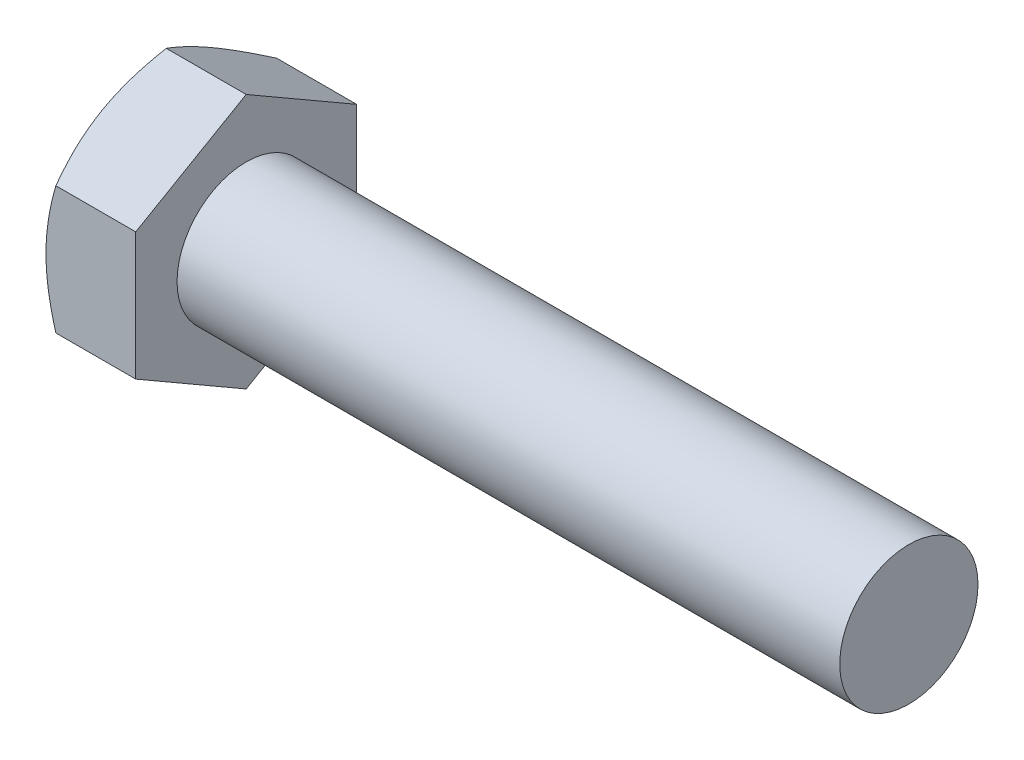
SolidWorks part; units mm, degrees
material "Alloy Steel"
ref_plane "Front Plane" through (0, 0, 0) normal (0, 0, 1) x (1, 0, 0)
ref_plane "Top Plane" through (0, 0, 0) normal (0, 1, 0) x (1, 0, 0)
ref_plane "Right Plane" through (0, 0, 0) normal (1, 0, 0) x (0, 0, -1)
sketch "Sketch1" plane through (0, 0, 0) normal (0, 0, 1) x (1, 0, 0)
  line L0 (-21.6297, 0) -> (21.6297, 0) construction
  line L1 (21.6297, 3.9751) -> (21.6297, -3.9751) construction
  line L2 (-16.4703, 6.35) -> (-16.4703, -6.35) construction
  line L3 (-21.6297, 6.35) -> (-21.6297, -6.35) construction
  point P9 (-16.4703, 0)
  point P10 (17.9255, -3.9751)
  point P11 (8.1359, 0)
  dimension "D1" = 3.7042
ref_plane "Plane2" through (21.6297, 0, 0) normal (1, 0, 0) x (0, 0, -1)
sketch "Sketch5" plane through (21.6297, 0, 0) normal (1, 0, 0) x (0, 0, -1)
  circle A0 centre (0, 0) radius 3.9751
extrude "Boss-Extrude3" add sketch "Sketch5" against normal up to vertex (38.1 mm away) up to point (-16.4703, 0, 0)
sketch "Sketch6" plane through (-16.4703, 0, 0) normal (-1, 0, 0) x (0, 0, 1)
  line L0 (0, 6.35) -> (0, -6.35) construction
  line L1 (6.35, 3.6662) -> (0, 7.3323)
  line L2 (0, 7.3323) -> (-6.35, 3.6662)
  line L3 (-6.35, 3.6662) -> (-6.35, -3.6662)
  line L4 (-6.35, -3.6662) -> (0, -7.3323)
  line L5 (0, -7.3323) -> (6.35, -3.6662)
  line L6 (6.35, -3.6662) -> (6.35, 3.6662)
  circle A0 centre (0, 0) radius 6.35 construction
extrude "Boss-Extrude4" add sketch "Sketch6" along normal up to vertex (5.1594 mm away) up to point (-21.6297, -6.35, 0)
sketch "Sketch7" plane through (-21.6297, 0, 0) normal (-1, 0, 0) x (0, 0, 1)
  circle A0 centre (0, 0) radius 6.35 construction
  circle A1 centre (0, 0) radius 6.35
sketch "Sketch12" plane through (-21.6297, 0, 0) normal (-1, 0, 0) x (0, 0, 1)
  line L0 (0, 4.8895) -> (0, 2.7305) construction
  line L1 (0.1905, 4.8895) -> (0.1905, 2.7305)
  line L2 (-0.1905, 4.8895) -> (-0.1905, 2.7305)
  line L3 (0, 3.9751) -> (0, -3.9751) construction
  arc A0 (0.1905, 4.8895) -> (-0.1905, 4.8895) centre (0, 4.8895) ccw
  arc A1 (-0.1905, 2.7305) -> (0.1905, 2.7305) centre (0, 2.7305) ccw
  circle A3 centre (0, 0) radius 2.54 construction
  circle A4 centre (0, 0) radius 5.08 construction
  point P2 (0, 3.81)
  dimension "D3" = 10.16
  dimension "D2" = 0.381
sketch "Sketch8" plane through (-21.6297, 0, 0) normal (-1, 0, 0) x (0, 0, 1)
  circle A0 centre (0, 0) radius 6.35 construction
  circle A1 centre (0, 0) radius 6.35
extrude "Cut-Extrude3" cut sketch "Sketch8" against normal through all draft 60 flip side to cut
sketch "Sketch13" plane through (0, 0, 0) normal (0, 0, 1) x (1, 0, 0)
  line L0 (17.2545, 0) -> (0, 0) construction
  circle A0 centre (17.2545, 0) radius 0.9652
  dimension "Hole Dia" = 1.9304
  dimension "Hole Distance" = 9.1186
extrude "Cotter Pin Hole" [suppressed] cut sketch "Sketch13" against normal through all and the other way through all
ref_plane "Split Plane" through (8.1359, 0, 0) normal (1, 0, 0) x (0, 0, -1)
ref_axis "Center Axis 1" through (-21.6297, 0, 0) along (1, 0, 0)
ref_plane "Contact Plane 1" through (-16.4703, 0, 0) normal (1, 0, 0) x (0, 0, -1)
split "Split1" [suppressed] bodies to split 118
sketch "Sketch9" [suppressed] plane through (22.8203, 0, 0) normal (1, 0, 0) x (0, 0, -1)
  circle A1 centre (0, 0) radius 3.9751
  circle A2 centre (0, 0) radius 3.9751
  dimension "D1" = 0
curve "Helix/Spiral1" [suppressed] pitch 1.0583 height 14.5521 turns 13.75 parameters "Pitch"=1.0583
chamfer "Chamfer1" [suppressed] distance 0.7938 angle 45
sketch "Sketch10" [suppressed] plane through (0, 0, 0) normal (0, 0, 1) x (1, 0, 0)
  line L0 (22.8203, 3.9751) -> (23.2172, 3.2877)
  line L1 (23.2172, 3.2877) -> (23.3495, 3.2877)
  line L2 (23.3495, 3.2877) -> (23.7464, 3.9751)
  line L3 (22.8203, 3.9751) -> (23.7464, 3.9751)
  line L4 (23.2833, 3.9751) -> (23.2833, 3.2877) construction
  line L5 (23.0188, 3.6314) -> (23.5479, 3.6314) construction
  dimension "D1" = 60
  dimension "D2" = 0.1323
  dimension "D3" = 0.5292
sweep "Cut-Sweep1" [suppressed] cut profiles "Sketch10" path "Helix/Spiral1"
sketch "Sketch15" [suppressed] plane through (9.3266, 0, 0) normal (1, 0, 0) x (0, 0, -1)
  circle A0 centre (0, 0) radius 3.9751 construction
  circle A1 centre (0, 0) radius 3.9751
extrude "Boss-Extrude5" [suppressed] add sketch "Sketch15" along normal through all draft 40
equation "\"D2@Sketch10\" = \"Pitch@Helix/Spiral1\"*.125"
equation "\"D3@Sketch10\" = \"Pitch@Helix/Spiral1\"*.5"
equation "\"D3@Helix/Spiral1\"=\"Min Thread@Sketch1\"+\"Pitch@Helix/Spiral1\""
equation "\"D1@Chamfer1\" = \"Pitch@Helix/Spiral1\"*.75"
equation "\"D1@Sketch12\" = \"Hex@Sketch1\"*.4"
equation "\"D3@Sketch12\" = \"Hex@Sketch1\"*.8"
equation "\"D2@Sketch12\" = \"Hex@Sketch1\"*.03"
equation "\"D1@Sketch1\" = \"Pitch@Helix/Spiral1\"*3.5"
